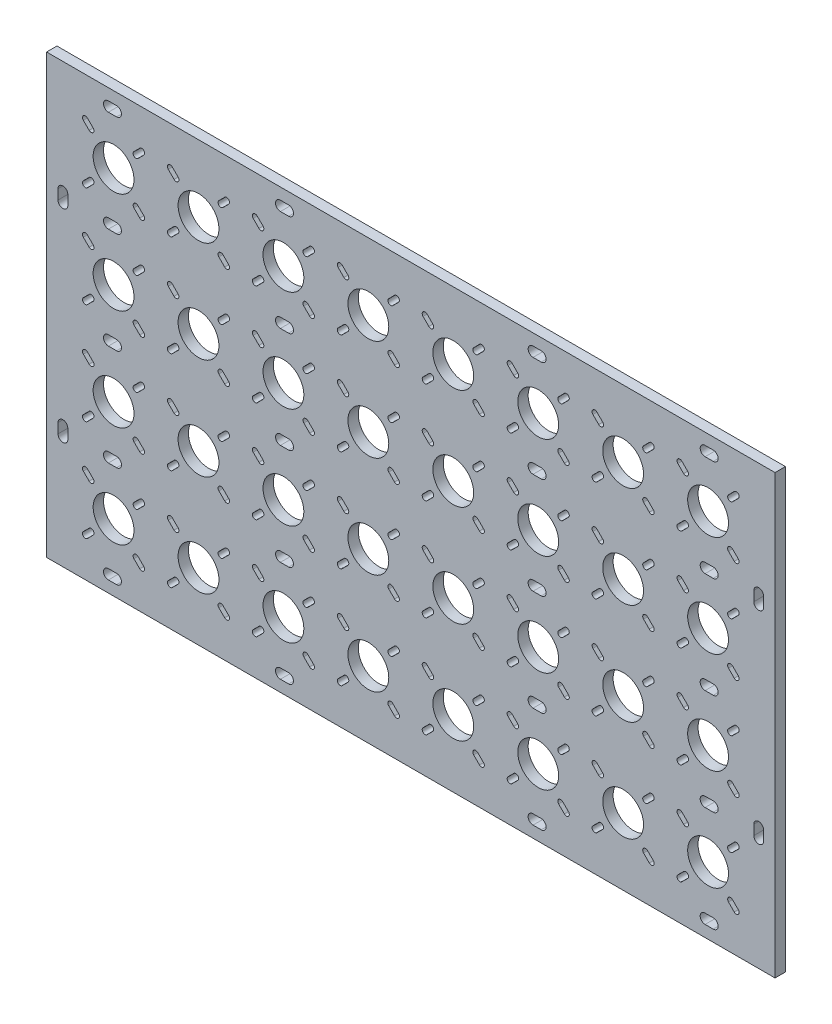
SolidWorks part; units mm, degrees
material "Acrylic (Medium-high impact)"
ref_plane "Front Plane" through (0, 0, 0) normal (0, 0, 1) x (1, 0, 0)
ref_plane "Top Plane" through (0, 0, 0) normal (0, 1, 0) x (1, 0, 0)
ref_plane "Right Plane" through (0, 0, 0) normal (1, 0, 0) x (0, 0, -1)
sketch "Sketch1" plane through (0, 0, 0) normal (0, 0, 1) x (1, 0, 0)
  line L0 (-203, 114) -> (-161, 72) construction
  line L1 (223, -134) -> (-223, -134)
  line L2 (223, -134) -> (223, 134)
  line L3 (223, 134) -> (-223, 134)
  line L4 (-223, -134) -> (-223, 134)
  line L5 (223, -134) -> (-223, 134) construction
  line L6 (223, 134) -> (-223, -134) construction
  line L7 (203, -114) -> (-203, -114) construction
  line L8 (203, -114) -> (203, 114) construction
  line L9 (203, 114) -> (-203, 114) construction
  line L10 (-203, -114) -> (-203, 114) construction
  line L11 (203, -114) -> (-203, 114) construction
  line L12 (203, 114) -> (-203, -114) construction
  line L13 (-203, 114) -> (-161, 114) construction
  line L14 (-203, 114) -> (-203, 72) construction
  line L15 (-203, 72) -> (-161, 72) construction
  line L16 (-161, 114) -> (-161, 72) construction
  line L17 (-203, 72) -> (-161, 114) construction
  line L18 (-199.2678, 110.2678) -> (-195.7322, 106.7322) construction
  line L19 (-166.5, 77.5) -> (-197.5, 77.5) construction
  line L20 (-166.5, 77.5) -> (-166.5, 108.5) construction
  line L21 (-166.5, 108.5) -> (-197.5, 108.5) construction
  line L22 (-197.5, 77.5) -> (-197.5, 108.5) construction
  line L23 (-166.5, 77.5) -> (-197.5, 108.5) construction
  line L24 (-166.5, 108.5) -> (-197.5, 77.5) construction
  line L25 (-198.0303, 111.5052) -> (-194.4948, 107.9697)
  line L26 (-200.5052, 109.0303) -> (-196.9697, 105.4948)
  line L27 (-164.7322, 110.2678) -> (-168.2678, 106.7322) construction
  line L28 (-163.4948, 109.0303) -> (-167.0303, 105.4948)
  line L29 (-165.9697, 111.5052) -> (-169.5052, 107.9697)
  line L30 (-164.7322, 75.7322) -> (-168.2678, 79.2678) construction
  line L31 (-165.9697, 74.4948) -> (-169.5052, 78.0303)
  line L32 (-163.4948, 76.9697) -> (-167.0303, 80.5052)
  line L33 (-199.2678, 75.7322) -> (-195.7322, 79.2678) construction
  line L34 (-200.5052, 76.9697) -> (-196.9697, 80.5052)
  line L35 (-198.0303, 74.4948) -> (-194.4948, 78.0303)
  line L36 (-109, 114) -> (-109, 72) construction
  line L37 (-151, 72) -> (-109, 72) construction
  line L38 (-147.2678, 110.2678) -> (-143.7322, 106.7322) construction
  line L39 (-146.0303, 111.5052) -> (-142.4948, 107.9697)
  line L40 (-148.5052, 109.0303) -> (-144.9697, 105.4948)
  line L41 (-112.7322, 110.2678) -> (-116.2678, 106.7322) construction
  line L42 (-111.4948, 109.0303) -> (-115.0303, 105.4948)
  line L43 (-113.9697, 111.5052) -> (-117.5052, 107.9697)
  line L44 (-112.7322, 75.7322) -> (-116.2678, 79.2678) construction
  line L45 (-113.9697, 74.4948) -> (-117.5052, 78.0303)
  line L46 (-111.4948, 76.9697) -> (-115.0303, 80.5052)
  line L47 (-147.2678, 75.7322) -> (-143.7322, 79.2678) construction
  line L48 (-148.5052, 76.9697) -> (-144.9697, 80.5052)
  line L49 (-146.0303, 74.4948) -> (-142.4948, 78.0303)
  line L50 (-57, 114) -> (-57, 72) construction
  line L51 (-99, 72) -> (-57, 72) construction
  line L52 (-95.2678, 110.2678) -> (-91.7322, 106.7322) construction
  line L53 (-94.0303, 111.5052) -> (-90.4948, 107.9697)
  line L54 (-96.5052, 109.0303) -> (-92.9697, 105.4948)
  line L55 (-60.7322, 110.2678) -> (-64.2678, 106.7322) construction
  line L56 (-59.4948, 109.0303) -> (-63.0303, 105.4948)
  line L57 (-61.9697, 111.5052) -> (-65.5052, 107.9697)
  line L58 (-60.7322, 75.7322) -> (-64.2678, 79.2678) construction
  line L59 (-61.9697, 74.4948) -> (-65.5052, 78.0303)
  line L60 (-59.4948, 76.9697) -> (-63.0303, 80.5052)
  line L61 (-95.2678, 75.7322) -> (-91.7322, 79.2678) construction
  line L62 (-96.5052, 76.9697) -> (-92.9697, 80.5052)
  line L63 (-94.0303, 74.4948) -> (-90.4948, 78.0303)
  line L64 (-5, 114) -> (-5, 72) construction
  line L65 (-47, 72) -> (-5, 72) construction
  line L66 (-43.2678, 110.2678) -> (-39.7322, 106.7322) construction
  line L67 (-42.0303, 111.5052) -> (-38.4948, 107.9697)
  line L68 (-44.5052, 109.0303) -> (-40.9697, 105.4948)
  line L69 (-8.7322, 110.2678) -> (-12.2678, 106.7322) construction
  line L70 (-7.4948, 109.0303) -> (-11.0303, 105.4948)
  line L71 (-9.9697, 111.5052) -> (-13.5052, 107.9697)
  line L72 (-8.7322, 75.7322) -> (-12.2678, 79.2678) construction
  line L73 (-9.9697, 74.4948) -> (-13.5052, 78.0303)
  line L74 (-7.4948, 76.9697) -> (-11.0303, 80.5052)
  line L75 (-43.2678, 75.7322) -> (-39.7322, 79.2678) construction
  line L76 (-44.5052, 76.9697) -> (-40.9697, 80.5052)
  line L77 (-42.0303, 74.4948) -> (-38.4948, 78.0303)
  line L78 (47, 114) -> (47, 72) construction
  line L79 (5, 72) -> (47, 72) construction
  line L80 (8.7322, 110.2678) -> (12.2678, 106.7322) construction
  line L81 (9.9697, 111.5052) -> (13.5052, 107.9697)
  line L82 (7.4948, 109.0303) -> (11.0303, 105.4948)
  line L83 (43.2678, 110.2678) -> (39.7322, 106.7322) construction
  line L84 (44.5052, 109.0303) -> (40.9697, 105.4948)
  line L85 (42.0303, 111.5052) -> (38.4948, 107.9697)
  line L86 (43.2678, 75.7322) -> (39.7322, 79.2678) construction
  line L87 (42.0303, 74.4948) -> (38.4948, 78.0303)
  line L88 (44.5052, 76.9697) -> (40.9697, 80.5052)
  line L89 (8.7322, 75.7322) -> (12.2678, 79.2678) construction
  line L90 (7.4948, 76.9697) -> (11.0303, 80.5052)
  line L91 (9.9697, 74.4948) -> (13.5052, 78.0303)
  line L92 (99, 114) -> (99, 72) construction
  line L93 (57, 72) -> (99, 72) construction
  line L94 (60.7322, 110.2678) -> (64.2678, 106.7322) construction
  line L95 (61.9697, 111.5052) -> (65.5052, 107.9697)
  line L96 (59.4948, 109.0303) -> (63.0303, 105.4948)
  line L97 (95.2678, 110.2678) -> (91.7322, 106.7322) construction
  line L98 (96.5052, 109.0303) -> (92.9697, 105.4948)
  line L99 (94.0303, 111.5052) -> (90.4948, 107.9697)
  line L100 (95.2678, 75.7322) -> (91.7322, 79.2678) construction
  line L101 (94.0303, 74.4948) -> (90.4948, 78.0303)
  line L102 (96.5052, 76.9697) -> (92.9697, 80.5052)
  line L103 (60.7322, 75.7322) -> (64.2678, 79.2678) construction
  line L104 (59.4948, 76.9697) -> (63.0303, 80.5052)
  line L105 (61.9697, 74.4948) -> (65.5052, 78.0303)
  line L106 (151, 114) -> (151, 72) construction
  line L107 (109, 72) -> (151, 72) construction
  line L108 (112.7322, 110.2678) -> (116.2678, 106.7322) construction
  line L109 (113.9697, 111.5052) -> (117.5052, 107.9697)
  line L110 (111.4948, 109.0303) -> (115.0303, 105.4948)
  line L111 (147.2678, 110.2678) -> (143.7322, 106.7322) construction
  line L112 (148.5052, 109.0303) -> (144.9697, 105.4948)
  line L113 (146.0303, 111.5052) -> (142.4948, 107.9697)
  line L114 (147.2678, 75.7322) -> (143.7322, 79.2678) construction
  line L115 (146.0303, 74.4948) -> (142.4948, 78.0303)
  line L116 (148.5052, 76.9697) -> (144.9697, 80.5052)
  line L117 (112.7322, 75.7322) -> (116.2678, 79.2678) construction
  line L118 (111.4948, 76.9697) -> (115.0303, 80.5052)
  line L119 (113.9697, 74.4948) -> (117.5052, 78.0303)
  line L120 (203, 114) -> (203, 72) construction
  line L121 (161, 72) -> (203, 72) construction
  line L122 (164.7322, 110.2678) -> (168.2678, 106.7322) construction
  line L123 (165.9697, 111.5052) -> (169.5052, 107.9697)
  line L124 (163.4948, 109.0303) -> (167.0303, 105.4948)
  line L125 (199.2678, 110.2678) -> (195.7322, 106.7322) construction
  line L126 (200.5052, 109.0303) -> (196.9697, 105.4948)
  line L127 (198.0303, 111.5052) -> (194.4948, 107.9697)
  line L128 (199.2678, 75.7322) -> (195.7322, 79.2678) construction
  line L129 (198.0303, 74.4948) -> (194.4948, 78.0303)
  line L130 (200.5052, 76.9697) -> (196.9697, 80.5052)
  line L131 (164.7322, 75.7322) -> (168.2678, 79.2678) construction
  line L132 (163.4948, 76.9697) -> (167.0303, 80.5052)
  line L133 (165.9697, 74.4948) -> (169.5052, 78.0303)
  line L134 (-109, 52) -> (-109, 10) construction
  line L135 (-151, 10) -> (-109, 10) construction
  line L136 (-147.2678, 48.2678) -> (-143.7322, 44.7322) construction
  line L137 (-146.0303, 49.5052) -> (-142.4948, 45.9697)
  line L138 (-148.5052, 47.0303) -> (-144.9697, 43.4948)
  line L139 (-112.7322, 48.2678) -> (-116.2678, 44.7322) construction
  line L140 (-111.4948, 47.0303) -> (-115.0303, 43.4948)
  line L141 (-113.9697, 49.5052) -> (-117.5052, 45.9697)
  line L142 (-112.7322, 13.7322) -> (-116.2678, 17.2678) construction
  line L143 (-113.9697, 12.4948) -> (-117.5052, 16.0303)
  line L144 (-111.4948, 14.9697) -> (-115.0303, 18.5052)
  line L145 (-147.2678, 13.7322) -> (-143.7322, 17.2678) construction
  line L146 (-148.5052, 14.9697) -> (-144.9697, 18.5052)
  line L147 (-146.0303, 12.4948) -> (-142.4948, 16.0303)
  line L148 (-57, 52) -> (-57, 10) construction
  line L149 (-99, 10) -> (-57, 10) construction
  line L150 (-95.2678, 48.2678) -> (-91.7322, 44.7322) construction
  line L151 (-94.0303, 49.5052) -> (-90.4948, 45.9697)
  line L152 (-96.5052, 47.0303) -> (-92.9697, 43.4948)
  line L153 (-60.7322, 48.2678) -> (-64.2678, 44.7322) construction
  line L154 (-59.4948, 47.0303) -> (-63.0303, 43.4948)
  line L155 (-61.9697, 49.5052) -> (-65.5052, 45.9697)
  line L156 (-60.7322, 13.7322) -> (-64.2678, 17.2678) construction
  line L157 (-61.9697, 12.4948) -> (-65.5052, 16.0303)
  line L158 (-59.4948, 14.9697) -> (-63.0303, 18.5052)
  line L159 (-95.2678, 13.7322) -> (-91.7322, 17.2678) construction
  line L160 (-96.5052, 14.9697) -> (-92.9697, 18.5052)
  line L161 (-94.0303, 12.4948) -> (-90.4948, 16.0303)
  line L162 (-5, 52) -> (-5, 10) construction
  line L163 (-47, 10) -> (-5, 10) construction
  line L164 (-43.2678, 48.2678) -> (-39.7322, 44.7322) construction
  line L165 (-42.0303, 49.5052) -> (-38.4948, 45.9697)
  line L166 (-44.5052, 47.0303) -> (-40.9697, 43.4948)
  line L167 (-8.7322, 48.2678) -> (-12.2678, 44.7322) construction
  line L168 (-7.4948, 47.0303) -> (-11.0303, 43.4948)
  line L169 (-9.9697, 49.5052) -> (-13.5052, 45.9697)
  line L170 (-8.7322, 13.7322) -> (-12.2678, 17.2678) construction
  line L171 (-9.9697, 12.4948) -> (-13.5052, 16.0303)
  line L172 (-7.4948, 14.9697) -> (-11.0303, 18.5052)
  line L173 (-43.2678, 13.7322) -> (-39.7322, 17.2678) construction
  line L174 (-44.5052, 14.9697) -> (-40.9697, 18.5052)
  line L175 (-42.0303, 12.4948) -> (-38.4948, 16.0303)
  line L176 (47, 52) -> (47, 10) construction
  line L177 (5, 10) -> (47, 10) construction
  line L178 (8.7322, 48.2678) -> (12.2678, 44.7322) construction
  line L179 (9.9697, 49.5052) -> (13.5052, 45.9697)
  line L180 (7.4948, 47.0303) -> (11.0303, 43.4948)
  line L181 (43.2678, 48.2678) -> (39.7322, 44.7322) construction
  line L182 (44.5052, 47.0303) -> (40.9697, 43.4948)
  line L183 (42.0303, 49.5052) -> (38.4948, 45.9697)
  line L184 (43.2678, 13.7322) -> (39.7322, 17.2678) construction
  line L185 (42.0303, 12.4948) -> (38.4948, 16.0303)
  line L186 (44.5052, 14.9697) -> (40.9697, 18.5052)
  line L187 (8.7322, 13.7322) -> (12.2678, 17.2678) construction
  line L188 (7.4948, 14.9697) -> (11.0303, 18.5052)
  line L189 (9.9697, 12.4948) -> (13.5052, 16.0303)
  line L190 (99, 52) -> (99, 10) construction
  line L191 (57, 10) -> (99, 10) construction
  line L192 (60.7322, 48.2678) -> (64.2678, 44.7322) construction
  line L193 (61.9697, 49.5052) -> (65.5052, 45.9697)
  line L194 (59.4948, 47.0303) -> (63.0303, 43.4948)
  line L195 (95.2678, 48.2678) -> (91.7322, 44.7322) construction
  line L196 (96.5052, 47.0303) -> (92.9697, 43.4948)
  line L197 (94.0303, 49.5052) -> (90.4948, 45.9697)
  line L198 (95.2678, 13.7322) -> (91.7322, 17.2678) construction
  line L199 (94.0303, 12.4948) -> (90.4948, 16.0303)
  line L200 (96.5052, 14.9697) -> (92.9697, 18.5052)
  line L201 (60.7322, 13.7322) -> (64.2678, 17.2678) construction
  line L202 (59.4948, 14.9697) -> (63.0303, 18.5052)
  line L203 (61.9697, 12.4948) -> (65.5052, 16.0303)
  line L204 (151, 52) -> (151, 10) construction
  line L205 (109, 10) -> (151, 10) construction
  line L206 (112.7322, 48.2678) -> (116.2678, 44.7322) construction
  line L207 (113.9697, 49.5052) -> (117.5052, 45.9697)
  line L208 (111.4948, 47.0303) -> (115.0303, 43.4948)
  line L209 (147.2678, 48.2678) -> (143.7322, 44.7322) construction
  line L210 (148.5052, 47.0303) -> (144.9697, 43.4948)
  line L211 (146.0303, 49.5052) -> (142.4948, 45.9697)
  line L212 (147.2678, 13.7322) -> (143.7322, 17.2678) construction
  line L213 (146.0303, 12.4948) -> (142.4948, 16.0303)
  line L214 (148.5052, 14.9697) -> (144.9697, 18.5052)
  line L215 (112.7322, 13.7322) -> (116.2678, 17.2678) construction
  line L216 (111.4948, 14.9697) -> (115.0303, 18.5052)
  line L217 (113.9697, 12.4948) -> (117.5052, 16.0303)
  line L218 (203, 52) -> (203, 10) construction
  line L219 (161, 10) -> (203, 10) construction
  line L220 (164.7322, 48.2678) -> (168.2678, 44.7322) construction
  line L221 (165.9697, 49.5052) -> (169.5052, 45.9697)
  line L222 (163.4948, 47.0303) -> (167.0303, 43.4948)
  line L223 (199.2678, 48.2678) -> (195.7322, 44.7322) construction
  line L224 (200.5052, 47.0303) -> (196.9697, 43.4948)
  line L225 (198.0303, 49.5052) -> (194.4948, 45.9697)
  line L226 (199.2678, 13.7322) -> (195.7322, 17.2678) construction
  line L227 (198.0303, 12.4948) -> (194.4948, 16.0303)
  line L228 (200.5052, 14.9697) -> (196.9697, 18.5052)
  line L229 (164.7322, 13.7322) -> (168.2678, 17.2678) construction
  line L230 (163.4948, 14.9697) -> (167.0303, 18.5052)
  line L231 (165.9697, 12.4948) -> (169.5052, 16.0303)
  line L232 (-109, -10) -> (-109, -52) construction
  line L233 (-151, -52) -> (-109, -52) construction
  line L234 (-147.2678, -13.7322) -> (-143.7322, -17.2678) construction
  line L235 (-146.0303, -12.4948) -> (-142.4948, -16.0303)
  line L236 (-148.5052, -14.9697) -> (-144.9697, -18.5052)
  line L237 (-112.7322, -13.7322) -> (-116.2678, -17.2678) construction
  line L238 (-111.4948, -14.9697) -> (-115.0303, -18.5052)
  line L239 (-113.9697, -12.4948) -> (-117.5052, -16.0303)
  line L240 (-112.7322, -48.2678) -> (-116.2678, -44.7322) construction
  line L241 (-113.9697, -49.5052) -> (-117.5052, -45.9697)
  line L242 (-111.4948, -47.0303) -> (-115.0303, -43.4948)
  line L243 (-147.2678, -48.2678) -> (-143.7322, -44.7322) construction
  line L244 (-148.5052, -47.0303) -> (-144.9697, -43.4948)
  line L245 (-146.0303, -49.5052) -> (-142.4948, -45.9697)
  line L246 (-57, -10) -> (-57, -52) construction
  line L247 (-99, -52) -> (-57, -52) construction
  line L248 (-95.2678, -13.7322) -> (-91.7322, -17.2678) construction
  line L249 (-94.0303, -12.4948) -> (-90.4948, -16.0303)
  line L250 (-96.5052, -14.9697) -> (-92.9697, -18.5052)
  line L251 (-60.7322, -13.7322) -> (-64.2678, -17.2678) construction
  line L252 (-59.4948, -14.9697) -> (-63.0303, -18.5052)
  line L253 (-61.9697, -12.4948) -> (-65.5052, -16.0303)
  line L254 (-60.7322, -48.2678) -> (-64.2678, -44.7322) construction
  line L255 (-61.9697, -49.5052) -> (-65.5052, -45.9697)
  line L256 (-59.4948, -47.0303) -> (-63.0303, -43.4948)
  line L257 (-95.2678, -48.2678) -> (-91.7322, -44.7322) construction
  line L258 (-96.5052, -47.0303) -> (-92.9697, -43.4948)
  line L259 (-94.0303, -49.5052) -> (-90.4948, -45.9697)
  line L260 (-5, -10) -> (-5, -52) construction
  line L261 (-47, -52) -> (-5, -52) construction
  line L262 (-43.2678, -13.7322) -> (-39.7322, -17.2678) construction
  line L263 (-42.0303, -12.4948) -> (-38.4948, -16.0303)
  line L264 (-44.5052, -14.9697) -> (-40.9697, -18.5052)
  line L265 (-8.7322, -13.7322) -> (-12.2678, -17.2678) construction
  line L266 (-7.4948, -14.9697) -> (-11.0303, -18.5052)
  line L267 (-9.9697, -12.4948) -> (-13.5052, -16.0303)
  line L268 (-8.7322, -48.2678) -> (-12.2678, -44.7322) construction
  line L269 (-9.9697, -49.5052) -> (-13.5052, -45.9697)
  line L270 (-7.4948, -47.0303) -> (-11.0303, -43.4948)
  line L271 (-43.2678, -48.2678) -> (-39.7322, -44.7322) construction
  line L272 (-44.5052, -47.0303) -> (-40.9697, -43.4948)
  line L273 (-42.0303, -49.5052) -> (-38.4948, -45.9697)
  line L274 (47, -10) -> (47, -52) construction
  line L275 (5, -52) -> (47, -52) construction
  line L276 (8.7322, -13.7322) -> (12.2678, -17.2678) construction
  line L277 (9.9697, -12.4948) -> (13.5052, -16.0303)
  line L278 (7.4948, -14.9697) -> (11.0303, -18.5052)
  line L279 (43.2678, -13.7322) -> (39.7322, -17.2678) construction
  line L280 (44.5052, -14.9697) -> (40.9697, -18.5052)
  line L281 (42.0303, -12.4948) -> (38.4948, -16.0303)
  line L282 (43.2678, -48.2678) -> (39.7322, -44.7322) construction
  line L283 (42.0303, -49.5052) -> (38.4948, -45.9697)
  line L284 (44.5052, -47.0303) -> (40.9697, -43.4948)
  line L285 (8.7322, -48.2678) -> (12.2678, -44.7322) construction
  line L286 (7.4948, -47.0303) -> (11.0303, -43.4948)
  line L287 (9.9697, -49.5052) -> (13.5052, -45.9697)
  line L288 (99, -10) -> (99, -52) construction
  line L289 (57, -52) -> (99, -52) construction
  line L290 (60.7322, -13.7322) -> (64.2678, -17.2678) construction
  line L291 (61.9697, -12.4948) -> (65.5052, -16.0303)
  line L292 (59.4948, -14.9697) -> (63.0303, -18.5052)
  line L293 (95.2678, -13.7322) -> (91.7322, -17.2678) construction
  line L294 (96.5052, -14.9697) -> (92.9697, -18.5052)
  line L295 (94.0303, -12.4948) -> (90.4948, -16.0303)
  line L296 (95.2678, -48.2678) -> (91.7322, -44.7322) construction
  line L297 (94.0303, -49.5052) -> (90.4948, -45.9697)
  line L298 (96.5052, -47.0303) -> (92.9697, -43.4948)
  line L299 (60.7322, -48.2678) -> (64.2678, -44.7322) construction
  line L300 (59.4948, -47.0303) -> (63.0303, -43.4948)
  line L301 (61.9697, -49.5052) -> (65.5052, -45.9697)
  line L302 (151, -10) -> (151, -52) construction
  line L303 (109, -52) -> (151, -52) construction
  line L304 (112.7322, -13.7322) -> (116.2678, -17.2678) construction
  line L305 (113.9697, -12.4948) -> (117.5052, -16.0303)
  line L306 (111.4948, -14.9697) -> (115.0303, -18.5052)
  line L307 (147.2678, -13.7322) -> (143.7322, -17.2678) construction
  line L308 (148.5052, -14.9697) -> (144.9697, -18.5052)
  line L309 (146.0303, -12.4948) -> (142.4948, -16.0303)
  line L310 (147.2678, -48.2678) -> (143.7322, -44.7322) construction
  line L311 (146.0303, -49.5052) -> (142.4948, -45.9697)
  line L312 (148.5052, -47.0303) -> (144.9697, -43.4948)
  line L313 (112.7322, -48.2678) -> (116.2678, -44.7322) construction
  line L314 (111.4948, -47.0303) -> (115.0303, -43.4948)
  line L315 (113.9697, -49.5052) -> (117.5052, -45.9697)
  line L316 (203, -10) -> (203, -52) construction
  line L317 (161, -52) -> (203, -52) construction
  line L318 (164.7322, -13.7322) -> (168.2678, -17.2678) construction
  line L319 (165.9697, -12.4948) -> (169.5052, -16.0303)
  line L320 (163.4948, -14.9697) -> (167.0303, -18.5052)
  line L321 (199.2678, -13.7322) -> (195.7322, -17.2678) construction
  line L322 (200.5052, -14.9697) -> (196.9697, -18.5052)
  line L323 (198.0303, -12.4948) -> (194.4948, -16.0303)
  line L324 (199.2678, -48.2678) -> (195.7322, -44.7322) construction
  line L325 (198.0303, -49.5052) -> (194.4948, -45.9697)
  line L326 (200.5052, -47.0303) -> (196.9697, -43.4948)
  line L327 (164.7322, -48.2678) -> (168.2678, -44.7322) construction
  line L328 (163.4948, -47.0303) -> (167.0303, -43.4948)
  line L329 (165.9697, -49.5052) -> (169.5052, -45.9697)
  line L330 (-109, -72) -> (-109, -114) construction
  line L331 (-151, -114) -> (-109, -114) construction
  line L332 (-147.2678, -75.7322) -> (-143.7322, -79.2678) construction
  line L333 (-146.0303, -74.4948) -> (-142.4948, -78.0303)
  line L334 (-148.5052, -76.9697) -> (-144.9697, -80.5052)
  line L335 (-112.7322, -75.7322) -> (-116.2678, -79.2678) construction
  line L336 (-111.4948, -76.9697) -> (-115.0303, -80.5052)
  line L337 (-113.9697, -74.4948) -> (-117.5052, -78.0303)
  line L338 (-112.7322, -110.2678) -> (-116.2678, -106.7322) construction
  line L339 (-113.9697, -111.5052) -> (-117.5052, -107.9697)
  line L340 (-111.4948, -109.0303) -> (-115.0303, -105.4948)
  line L341 (-147.2678, -110.2678) -> (-143.7322, -106.7322) construction
  line L342 (-148.5052, -109.0303) -> (-144.9697, -105.4948)
  line L343 (-146.0303, -111.5052) -> (-142.4948, -107.9697)
  line L344 (-57, -72) -> (-57, -114) construction
  line L345 (-99, -114) -> (-57, -114) construction
  line L346 (-95.2678, -75.7322) -> (-91.7322, -79.2678) construction
  line L347 (-94.0303, -74.4948) -> (-90.4948, -78.0303)
  line L348 (-96.5052, -76.9697) -> (-92.9697, -80.5052)
  line L349 (-60.7322, -75.7322) -> (-64.2678, -79.2678) construction
  line L350 (-59.4948, -76.9697) -> (-63.0303, -80.5052)
  line L351 (-61.9697, -74.4948) -> (-65.5052, -78.0303)
  line L352 (-60.7322, -110.2678) -> (-64.2678, -106.7322) construction
  line L353 (-61.9697, -111.5052) -> (-65.5052, -107.9697)
  line L354 (-59.4948, -109.0303) -> (-63.0303, -105.4948)
  line L355 (-95.2678, -110.2678) -> (-91.7322, -106.7322) construction
  line L356 (-96.5052, -109.0303) -> (-92.9697, -105.4948)
  line L357 (-94.0303, -111.5052) -> (-90.4948, -107.9697)
  line L358 (-5, -72) -> (-5, -114) construction
  line L359 (-47, -114) -> (-5, -114) construction
  line L360 (-43.2678, -75.7322) -> (-39.7322, -79.2678) construction
  line L361 (-42.0303, -74.4948) -> (-38.4948, -78.0303)
  line L362 (-44.5052, -76.9697) -> (-40.9697, -80.5052)
  line L363 (-8.7322, -75.7322) -> (-12.2678, -79.2678) construction
  line L364 (-7.4948, -76.9697) -> (-11.0303, -80.5052)
  line L365 (-9.9697, -74.4948) -> (-13.5052, -78.0303)
  line L366 (-8.7322, -110.2678) -> (-12.2678, -106.7322) construction
  line L367 (-9.9697, -111.5052) -> (-13.5052, -107.9697)
  line L368 (-7.4948, -109.0303) -> (-11.0303, -105.4948)
  line L369 (-43.2678, -110.2678) -> (-39.7322, -106.7322) construction
  line L370 (-44.5052, -109.0303) -> (-40.9697, -105.4948)
  line L371 (-42.0303, -111.5052) -> (-38.4948, -107.9697)
  line L372 (47, -72) -> (47, -114) construction
  line L373 (5, -114) -> (47, -114) construction
  line L374 (8.7322, -75.7322) -> (12.2678, -79.2678) construction
  line L375 (9.9697, -74.4948) -> (13.5052, -78.0303)
  line L376 (7.4948, -76.9697) -> (11.0303, -80.5052)
  line L377 (43.2678, -75.7322) -> (39.7322, -79.2678) construction
  line L378 (44.5052, -76.9697) -> (40.9697, -80.5052)
  line L379 (42.0303, -74.4948) -> (38.4948, -78.0303)
  line L380 (43.2678, -110.2678) -> (39.7322, -106.7322) construction
  line L381 (42.0303, -111.5052) -> (38.4948, -107.9697)
  line L382 (44.5052, -109.0303) -> (40.9697, -105.4948)
  line L383 (8.7322, -110.2678) -> (12.2678, -106.7322) construction
  line L384 (7.4948, -109.0303) -> (11.0303, -105.4948)
  line L385 (9.9697, -111.5052) -> (13.5052, -107.9697)
  line L386 (99, -72) -> (99, -114) construction
  line L387 (57, -114) -> (99, -114) construction
  line L388 (60.7322, -75.7322) -> (64.2678, -79.2678) construction
  line L389 (61.9697, -74.4948) -> (65.5052, -78.0303)
  line L390 (59.4948, -76.9697) -> (63.0303, -80.5052)
  line L391 (95.2678, -75.7322) -> (91.7322, -79.2678) construction
  line L392 (96.5052, -76.9697) -> (92.9697, -80.5052)
  line L393 (94.0303, -74.4948) -> (90.4948, -78.0303)
  line L394 (95.2678, -110.2678) -> (91.7322, -106.7322) construction
  line L395 (94.0303, -111.5052) -> (90.4948, -107.9697)
  line L396 (96.5052, -109.0303) -> (92.9697, -105.4948)
  line L397 (60.7322, -110.2678) -> (64.2678, -106.7322) construction
  line L398 (59.4948, -109.0303) -> (63.0303, -105.4948)
  line L399 (61.9697, -111.5052) -> (65.5052, -107.9697)
  line L400 (151, -72) -> (151, -114) construction
  line L401 (109, -114) -> (151, -114) construction
  line L402 (112.7322, -75.7322) -> (116.2678, -79.2678) construction
  line L403 (113.9697, -74.4948) -> (117.5052, -78.0303)
  line L404 (111.4948, -76.9697) -> (115.0303, -80.5052)
  line L405 (147.2678, -75.7322) -> (143.7322, -79.2678) construction
  line L406 (148.5052, -76.9697) -> (144.9697, -80.5052)
  line L407 (146.0303, -74.4948) -> (142.4948, -78.0303)
  line L408 (147.2678, -110.2678) -> (143.7322, -106.7322) construction
  line L409 (146.0303, -111.5052) -> (142.4948, -107.9697)
  line L410 (148.5052, -109.0303) -> (144.9697, -105.4948)
  line L411 (112.7322, -110.2678) -> (116.2678, -106.7322) construction
  line L412 (111.4948, -109.0303) -> (115.0303, -105.4948)
  line L413 (113.9697, -111.5052) -> (117.5052, -107.9697)
  line L414 (203, -72) -> (203, -114) construction
  line L415 (161, -114) -> (203, -114) construction
  line L416 (164.7322, -75.7322) -> (168.2678, -79.2678) construction
  line L417 (165.9697, -74.4948) -> (169.5052, -78.0303)
  line L418 (163.4948, -76.9697) -> (167.0303, -80.5052)
  line L419 (199.2678, -75.7322) -> (195.7322, -79.2678) construction
  line L420 (200.5052, -76.9697) -> (196.9697, -80.5052)
  line L421 (198.0303, -74.4948) -> (194.4948, -78.0303)
  line L422 (199.2678, -110.2678) -> (195.7322, -106.7322) construction
  line L423 (198.0303, -111.5052) -> (194.4948, -107.9697)
  line L424 (200.5052, -109.0303) -> (196.9697, -105.4948)
  line L425 (164.7322, -110.2678) -> (168.2678, -106.7322) construction
  line L426 (163.4948, -109.0303) -> (167.0303, -105.4948)
  line L427 (165.9697, -111.5052) -> (169.5052, -107.9697)
  line L428 (-161, 52) -> (-161, 10) construction
  line L429 (-203, 10) -> (-161, 10) construction
  line L430 (-199.2678, 48.2678) -> (-195.7322, 44.7322) construction
  line L431 (-198.0303, 49.5052) -> (-194.4948, 45.9697)
  line L432 (-200.5052, 47.0303) -> (-196.9697, 43.4948)
  line L433 (-164.7322, 48.2678) -> (-168.2678, 44.7322) construction
  line L434 (-163.4948, 47.0303) -> (-167.0303, 43.4948)
  line L435 (-165.9697, 49.5052) -> (-169.5052, 45.9697)
  line L436 (-164.7322, 13.7322) -> (-168.2678, 17.2678) construction
  line L437 (-165.9697, 12.4948) -> (-169.5052, 16.0303)
  line L438 (-163.4948, 14.9697) -> (-167.0303, 18.5052)
  line L439 (-199.2678, 13.7322) -> (-195.7322, 17.2678) construction
  line L440 (-200.5052, 14.9697) -> (-196.9697, 18.5052)
  line L441 (-198.0303, 12.4948) -> (-194.4948, 16.0303)
  line L442 (-161, -10) -> (-161, -52) construction
  line L443 (-203, -52) -> (-161, -52) construction
  line L444 (-199.2678, -13.7322) -> (-195.7322, -17.2678) construction
  line L445 (-198.0303, -12.4948) -> (-194.4948, -16.0303)
  line L446 (-200.5052, -14.9697) -> (-196.9697, -18.5052)
  line L447 (-164.7322, -13.7322) -> (-168.2678, -17.2678) construction
  line L448 (-163.4948, -14.9697) -> (-167.0303, -18.5052)
  line L449 (-165.9697, -12.4948) -> (-169.5052, -16.0303)
  line L450 (-164.7322, -48.2678) -> (-168.2678, -44.7322) construction
  line L451 (-165.9697, -49.5052) -> (-169.5052, -45.9697)
  line L452 (-163.4948, -47.0303) -> (-167.0303, -43.4948)
  line L453 (-199.2678, -48.2678) -> (-195.7322, -44.7322) construction
  line L454 (-200.5052, -47.0303) -> (-196.9697, -43.4948)
  line L455 (-198.0303, -49.5052) -> (-194.4948, -45.9697)
  line L456 (-161, -72) -> (-161, -114) construction
  line L457 (-203, -114) -> (-161, -114) construction
  line L458 (-199.2678, -75.7322) -> (-195.7322, -79.2678) construction
  line L459 (-198.0303, -74.4948) -> (-194.4948, -78.0303)
  line L460 (-200.5052, -76.9697) -> (-196.9697, -80.5052)
  line L461 (-164.7322, -75.7322) -> (-168.2678, -79.2678) construction
  line L462 (-163.4948, -76.9697) -> (-167.0303, -80.5052)
  line L463 (-165.9697, -74.4948) -> (-169.5052, -78.0303)
  line L464 (-164.7322, -110.2678) -> (-168.2678, -106.7322) construction
  line L465 (-165.9697, -111.5052) -> (-169.5052, -107.9697)
  line L466 (-163.4948, -109.0303) -> (-167.0303, -105.4948)
  line L467 (-199.2678, -110.2678) -> (-195.7322, -106.7322) construction
  line L468 (-200.5052, -109.0303) -> (-196.9697, -105.4948)
  line L469 (-198.0303, -111.5052) -> (-194.4948, -107.9697)
  line L470 (-185.1645, 124) -> (-180.1645, 124) construction
  line L471 (213, -124) -> (-213, -124) construction
  line L472 (213, -124) -> (213, 124) construction
  line L473 (213, 124) -> (-213, 124) construction
  line L474 (-213, -124) -> (-213, 124) construction
  line L475 (213, -124) -> (-213, 124) construction
  line L476 (213, 124) -> (-213, -124) construction
  line L477 (-185.1645, 127) -> (-180.1645, 127)
  line L478 (-185.1645, 121) -> (-180.1645, 121)
  line L479 (-182, 93) -> (-182, 88.4154) construction
  line L480 (-182, 93) -> (-177.9536, 93) construction
  line L481 (-130, 93) -> (-130, 88.4154) construction
  line L482 (-74.8355, 124) -> (-79.8355, 124) construction
  line L483 (-74.8355, 127) -> (-79.8355, 127)
  line L484 (-74.8355, 121) -> (-79.8355, 121)
  line L485 (0, 10) -> (0, -7.4331) construction
  line L486 (-7.4948, 0) -> (6.3552, 0) construction
  line L487 (74.8355, 124) -> (79.8355, 124) construction
  line L488 (74.8355, 127) -> (79.8355, 127)
  line L489 (74.8355, 121) -> (79.8355, 121)
  line L490 (185.1645, 124) -> (180.1645, 124) construction
  line L491 (185.1645, 127) -> (180.1645, 127)
  line L492 (185.1645, 121) -> (180.1645, 121)
  line L493 (185.1645, 62) -> (180.1645, 62) construction
  line L494 (185.1645, 59) -> (180.1645, 59)
  line L495 (185.1645, 65) -> (180.1645, 65)
  line L496 (74.8355, 62) -> (79.8355, 62) construction
  line L497 (74.8355, 59) -> (79.8355, 59)
  line L498 (74.8355, 65) -> (79.8355, 65)
  line L499 (-74.8355, 62) -> (-79.8355, 62) construction
  line L500 (-74.8355, 59) -> (-79.8355, 59)
  line L501 (-74.8355, 65) -> (-79.8355, 65)
  line L502 (-185.1645, 62) -> (-180.1645, 62) construction
  line L503 (-185.1645, 59) -> (-180.1645, 59)
  line L504 (-185.1645, 65) -> (-180.1645, 65)
  line L505 (-182, 31) -> (-176.1897, 31) construction
  line L506 (185.1645, 0) -> (180.1645, 0) construction
  line L507 (185.1645, 3) -> (180.1645, 3)
  line L508 (185.1645, -3) -> (180.1645, -3)
  line L509 (74.8355, 0) -> (79.8355, 0) construction
  line L510 (74.8355, 3) -> (79.8355, 3)
  line L511 (74.8355, -3) -> (79.8355, -3)
  line L512 (-74.8355, 0) -> (-79.8355, 0) construction
  line L513 (-74.8355, 3) -> (-79.8355, 3)
  line L514 (-74.8355, -3) -> (-79.8355, -3)
  line L515 (-185.1645, 0) -> (-180.1645, 0) construction
  line L516 (-185.1645, 3) -> (-180.1645, 3)
  line L517 (-185.1645, -3) -> (-180.1645, -3)
  line L518 (185.1645, -62) -> (180.1645, -62) construction
  line L519 (185.1645, -59) -> (180.1645, -59)
  line L520 (185.1645, -65) -> (180.1645, -65)
  line L521 (74.8355, -62) -> (79.8355, -62) construction
  line L522 (74.8355, -59) -> (79.8355, -59)
  line L523 (74.8355, -65) -> (79.8355, -65)
  line L524 (-74.8355, -62) -> (-79.8355, -62) construction
  line L525 (-74.8355, -59) -> (-79.8355, -59)
  line L526 (-74.8355, -65) -> (-79.8355, -65)
  line L527 (-185.1645, -62) -> (-180.1645, -62) construction
  line L528 (-185.1645, -59) -> (-180.1645, -59)
  line L529 (-185.1645, -65) -> (-180.1645, -65)
  line L530 (185.1645, -124) -> (180.1645, -124) construction
  line L531 (185.1645, -127) -> (180.1645, -127)
  line L532 (185.1645, -121) -> (180.1645, -121)
  line L533 (74.8355, -124) -> (79.8355, -124) construction
  line L534 (74.8355, -127) -> (79.8355, -127)
  line L535 (74.8355, -121) -> (79.8355, -121)
  line L536 (-74.8355, -124) -> (-79.8355, -124) construction
  line L537 (-74.8355, -127) -> (-79.8355, -127)
  line L538 (-74.8355, -121) -> (-79.8355, -121)
  line L539 (-185.1645, -124) -> (-180.1645, -124) construction
  line L540 (-185.1645, -127) -> (-180.1645, -127)
  line L541 (-185.1645, -121) -> (-180.1645, -121)
  line L542 (-213, 59) -> (-213, 65) construction
  line L543 (-216, 59) -> (-216, 65)
  line L544 (-210, 59) -> (-210, 65)
  line L545 (-213, -59) -> (-213, -65) construction
  line L546 (-216, -59) -> (-216, -65)
  line L547 (-210, -59) -> (-210, -65)
  line L548 (213, 59) -> (213, 65) construction
  line L549 (216, 59) -> (216, 65)
  line L550 (210, 59) -> (210, 65)
  line L551 (213, -59) -> (213, -65) construction
  line L552 (216, -59) -> (216, -65)
  line L553 (210, -59) -> (210, -65)
  circle A0 centre (-182, 93) radius 12.5
  arc A5 (-198.0303, 111.5052) -> (-200.5052, 109.0303) centre (-199.2678, 110.2678) ccw
  arc A6 (-196.9697, 105.4948) -> (-194.4948, 107.9697) centre (-195.7322, 106.7322) ccw
  arc A7 (-163.4948, 109.0303) -> (-165.9697, 111.5052) centre (-164.7322, 110.2678) ccw
  arc A8 (-169.5052, 107.9697) -> (-167.0303, 105.4948) centre (-168.2678, 106.7322) ccw
  arc A9 (-165.9697, 74.4948) -> (-163.4948, 76.9697) centre (-164.7322, 75.7322) ccw
  arc A10 (-167.0303, 80.5052) -> (-169.5052, 78.0303) centre (-168.2678, 79.2678) ccw
  arc A11 (-200.5052, 76.9697) -> (-198.0303, 74.4948) centre (-199.2678, 75.7322) ccw
  arc A12 (-194.4948, 78.0303) -> (-196.9697, 80.5052) centre (-195.7322, 79.2678) ccw
  circle A13 centre (-130, 93) radius 12.5
  arc A14 (-146.0303, 111.5052) -> (-148.5052, 109.0303) centre (-147.2678, 110.2678) ccw
  arc A15 (-144.9697, 105.4948) -> (-142.4948, 107.9697) centre (-143.7322, 106.7322) ccw
  arc A16 (-111.4948, 109.0303) -> (-113.9697, 111.5052) centre (-112.7322, 110.2678) ccw
  arc A17 (-117.5052, 107.9697) -> (-115.0303, 105.4948) centre (-116.2678, 106.7322) ccw
  arc A18 (-113.9697, 74.4948) -> (-111.4948, 76.9697) centre (-112.7322, 75.7322) ccw
  arc A19 (-115.0303, 80.5052) -> (-117.5052, 78.0303) centre (-116.2678, 79.2678) ccw
  arc A20 (-148.5052, 76.9697) -> (-146.0303, 74.4948) centre (-147.2678, 75.7322) ccw
  arc A21 (-142.4948, 78.0303) -> (-144.9697, 80.5052) centre (-143.7322, 79.2678) ccw
  circle A22 centre (-78, 93) radius 12.5
  arc A23 (-94.0303, 111.5052) -> (-96.5052, 109.0303) centre (-95.2678, 110.2678) ccw
  arc A24 (-92.9697, 105.4948) -> (-90.4948, 107.9697) centre (-91.7322, 106.7322) ccw
  arc A25 (-59.4948, 109.0303) -> (-61.9697, 111.5052) centre (-60.7322, 110.2678) ccw
  arc A26 (-65.5052, 107.9697) -> (-63.0303, 105.4948) centre (-64.2678, 106.7322) ccw
  arc A27 (-61.9697, 74.4948) -> (-59.4948, 76.9697) centre (-60.7322, 75.7322) ccw
  arc A28 (-63.0303, 80.5052) -> (-65.5052, 78.0303) centre (-64.2678, 79.2678) ccw
  arc A29 (-96.5052, 76.9697) -> (-94.0303, 74.4948) centre (-95.2678, 75.7322) ccw
  arc A30 (-90.4948, 78.0303) -> (-92.9697, 80.5052) centre (-91.7322, 79.2678) ccw
  circle A31 centre (-26, 93) radius 12.5
  arc A32 (-42.0303, 111.5052) -> (-44.5052, 109.0303) centre (-43.2678, 110.2678) ccw
  arc A33 (-40.9697, 105.4948) -> (-38.4948, 107.9697) centre (-39.7322, 106.7322) ccw
  arc A34 (-7.4948, 109.0303) -> (-9.9697, 111.5052) centre (-8.7322, 110.2678) ccw
  arc A35 (-13.5052, 107.9697) -> (-11.0303, 105.4948) centre (-12.2678, 106.7322) ccw
  arc A36 (-9.9697, 74.4948) -> (-7.4948, 76.9697) centre (-8.7322, 75.7322) ccw
  arc A37 (-11.0303, 80.5052) -> (-13.5052, 78.0303) centre (-12.2678, 79.2678) ccw
  arc A38 (-44.5052, 76.9697) -> (-42.0303, 74.4948) centre (-43.2678, 75.7322) ccw
  arc A39 (-38.4948, 78.0303) -> (-40.9697, 80.5052) centre (-39.7322, 79.2678) ccw
  circle A40 centre (26, 93) radius 12.5
  arc A41 (9.9697, 111.5052) -> (7.4948, 109.0303) centre (8.7322, 110.2678) ccw
  arc A42 (11.0303, 105.4948) -> (13.5052, 107.9697) centre (12.2678, 106.7322) ccw
  arc A43 (44.5052, 109.0303) -> (42.0303, 111.5052) centre (43.2678, 110.2678) ccw
  arc A44 (38.4948, 107.9697) -> (40.9697, 105.4948) centre (39.7322, 106.7322) ccw
  arc A45 (42.0303, 74.4948) -> (44.5052, 76.9697) centre (43.2678, 75.7322) ccw
  arc A46 (40.9697, 80.5052) -> (38.4948, 78.0303) centre (39.7322, 79.2678) ccw
  arc A47 (7.4948, 76.9697) -> (9.9697, 74.4948) centre (8.7322, 75.7322) ccw
  arc A48 (13.5052, 78.0303) -> (11.0303, 80.5052) centre (12.2678, 79.2678) ccw
  circle A49 centre (78, 93) radius 12.5
  arc A50 (61.9697, 111.5052) -> (59.4948, 109.0303) centre (60.7322, 110.2678) ccw
  arc A51 (63.0303, 105.4948) -> (65.5052, 107.9697) centre (64.2678, 106.7322) ccw
  arc A52 (96.5052, 109.0303) -> (94.0303, 111.5052) centre (95.2678, 110.2678) ccw
  arc A53 (90.4948, 107.9697) -> (92.9697, 105.4948) centre (91.7322, 106.7322) ccw
  arc A54 (94.0303, 74.4948) -> (96.5052, 76.9697) centre (95.2678, 75.7322) ccw
  arc A55 (92.9697, 80.5052) -> (90.4948, 78.0303) centre (91.7322, 79.2678) ccw
  arc A56 (59.4948, 76.9697) -> (61.9697, 74.4948) centre (60.7322, 75.7322) ccw
  arc A57 (65.5052, 78.0303) -> (63.0303, 80.5052) centre (64.2678, 79.2678) ccw
  circle A58 centre (130, 93) radius 12.5
  arc A59 (113.9697, 111.5052) -> (111.4948, 109.0303) centre (112.7322, 110.2678) ccw
  arc A60 (115.0303, 105.4948) -> (117.5052, 107.9697) centre (116.2678, 106.7322) ccw
  arc A61 (148.5052, 109.0303) -> (146.0303, 111.5052) centre (147.2678, 110.2678) ccw
  arc A62 (142.4948, 107.9697) -> (144.9697, 105.4948) centre (143.7322, 106.7322) ccw
  arc A63 (146.0303, 74.4948) -> (148.5052, 76.9697) centre (147.2678, 75.7322) ccw
  arc A64 (144.9697, 80.5052) -> (142.4948, 78.0303) centre (143.7322, 79.2678) ccw
  arc A65 (111.4948, 76.9697) -> (113.9697, 74.4948) centre (112.7322, 75.7322) ccw
  arc A66 (117.5052, 78.0303) -> (115.0303, 80.5052) centre (116.2678, 79.2678) ccw
  circle A67 centre (182, 93) radius 12.5
  arc A68 (165.9697, 111.5052) -> (163.4948, 109.0303) centre (164.7322, 110.2678) ccw
  arc A69 (167.0303, 105.4948) -> (169.5052, 107.9697) centre (168.2678, 106.7322) ccw
  arc A70 (200.5052, 109.0303) -> (198.0303, 111.5052) centre (199.2678, 110.2678) ccw
  arc A71 (194.4948, 107.9697) -> (196.9697, 105.4948) centre (195.7322, 106.7322) ccw
  arc A72 (198.0303, 74.4948) -> (200.5052, 76.9697) centre (199.2678, 75.7322) ccw
  arc A73 (196.9697, 80.5052) -> (194.4948, 78.0303) centre (195.7322, 79.2678) ccw
  arc A74 (163.4948, 76.9697) -> (165.9697, 74.4948) centre (164.7322, 75.7322) ccw
  arc A75 (169.5052, 78.0303) -> (167.0303, 80.5052) centre (168.2678, 79.2678) ccw
  circle A76 centre (-130, 31) radius 12.5
  arc A77 (-146.0303, 49.5052) -> (-148.5052, 47.0303) centre (-147.2678, 48.2678) ccw
  arc A78 (-144.9697, 43.4948) -> (-142.4948, 45.9697) centre (-143.7322, 44.7322) ccw
  arc A79 (-111.4948, 47.0303) -> (-113.9697, 49.5052) centre (-112.7322, 48.2678) ccw
  arc A80 (-117.5052, 45.9697) -> (-115.0303, 43.4948) centre (-116.2678, 44.7322) ccw
  arc A81 (-113.9697, 12.4948) -> (-111.4948, 14.9697) centre (-112.7322, 13.7322) ccw
  arc A82 (-115.0303, 18.5052) -> (-117.5052, 16.0303) centre (-116.2678, 17.2678) ccw
  arc A83 (-148.5052, 14.9697) -> (-146.0303, 12.4948) centre (-147.2678, 13.7322) ccw
  arc A84 (-142.4948, 16.0303) -> (-144.9697, 18.5052) centre (-143.7322, 17.2678) ccw
  circle A85 centre (-78, 31) radius 12.5
  arc A86 (-94.0303, 49.5052) -> (-96.5052, 47.0303) centre (-95.2678, 48.2678) ccw
  arc A87 (-92.9697, 43.4948) -> (-90.4948, 45.9697) centre (-91.7322, 44.7322) ccw
  arc A88 (-59.4948, 47.0303) -> (-61.9697, 49.5052) centre (-60.7322, 48.2678) ccw
  arc A89 (-65.5052, 45.9697) -> (-63.0303, 43.4948) centre (-64.2678, 44.7322) ccw
  arc A90 (-61.9697, 12.4948) -> (-59.4948, 14.9697) centre (-60.7322, 13.7322) ccw
  arc A91 (-63.0303, 18.5052) -> (-65.5052, 16.0303) centre (-64.2678, 17.2678) ccw
  arc A92 (-96.5052, 14.9697) -> (-94.0303, 12.4948) centre (-95.2678, 13.7322) ccw
  arc A93 (-90.4948, 16.0303) -> (-92.9697, 18.5052) centre (-91.7322, 17.2678) ccw
  circle A94 centre (-26, 31) radius 12.5
  arc A95 (-42.0303, 49.5052) -> (-44.5052, 47.0303) centre (-43.2678, 48.2678) ccw
  arc A96 (-40.9697, 43.4948) -> (-38.4948, 45.9697) centre (-39.7322, 44.7322) ccw
  arc A97 (-7.4948, 47.0303) -> (-9.9697, 49.5052) centre (-8.7322, 48.2678) ccw
  arc A98 (-13.5052, 45.9697) -> (-11.0303, 43.4948) centre (-12.2678, 44.7322) ccw
  arc A99 (-9.9697, 12.4948) -> (-7.4948, 14.9697) centre (-8.7322, 13.7322) ccw
  arc A100 (-11.0303, 18.5052) -> (-13.5052, 16.0303) centre (-12.2678, 17.2678) ccw
  arc A101 (-44.5052, 14.9697) -> (-42.0303, 12.4948) centre (-43.2678, 13.7322) ccw
  arc A102 (-38.4948, 16.0303) -> (-40.9697, 18.5052) centre (-39.7322, 17.2678) ccw
  circle A103 centre (26, 31) radius 12.5
  arc A104 (9.9697, 49.5052) -> (7.4948, 47.0303) centre (8.7322, 48.2678) ccw
  arc A105 (11.0303, 43.4948) -> (13.5052, 45.9697) centre (12.2678, 44.7322) ccw
  arc A106 (44.5052, 47.0303) -> (42.0303, 49.5052) centre (43.2678, 48.2678) ccw
  arc A107 (38.4948, 45.9697) -> (40.9697, 43.4948) centre (39.7322, 44.7322) ccw
  arc A108 (42.0303, 12.4948) -> (44.5052, 14.9697) centre (43.2678, 13.7322) ccw
  arc A109 (40.9697, 18.5052) -> (38.4948, 16.0303) centre (39.7322, 17.2678) ccw
  arc A110 (7.4948, 14.9697) -> (9.9697, 12.4948) centre (8.7322, 13.7322) ccw
  arc A111 (13.5052, 16.0303) -> (11.0303, 18.5052) centre (12.2678, 17.2678) ccw
  circle A112 centre (78, 31) radius 12.5
  arc A113 (61.9697, 49.5052) -> (59.4948, 47.0303) centre (60.7322, 48.2678) ccw
  arc A114 (63.0303, 43.4948) -> (65.5052, 45.9697) centre (64.2678, 44.7322) ccw
  arc A115 (96.5052, 47.0303) -> (94.0303, 49.5052) centre (95.2678, 48.2678) ccw
  arc A116 (90.4948, 45.9697) -> (92.9697, 43.4948) centre (91.7322, 44.7322) ccw
  arc A117 (94.0303, 12.4948) -> (96.5052, 14.9697) centre (95.2678, 13.7322) ccw
  arc A118 (92.9697, 18.5052) -> (90.4948, 16.0303) centre (91.7322, 17.2678) ccw
  arc A119 (59.4948, 14.9697) -> (61.9697, 12.4948) centre (60.7322, 13.7322) ccw
  arc A120 (65.5052, 16.0303) -> (63.0303, 18.5052) centre (64.2678, 17.2678) ccw
  circle A121 centre (130, 31) radius 12.5
  arc A122 (113.9697, 49.5052) -> (111.4948, 47.0303) centre (112.7322, 48.2678) ccw
  arc A123 (115.0303, 43.4948) -> (117.5052, 45.9697) centre (116.2678, 44.7322) ccw
  arc A124 (148.5052, 47.0303) -> (146.0303, 49.5052) centre (147.2678, 48.2678) ccw
  arc A125 (142.4948, 45.9697) -> (144.9697, 43.4948) centre (143.7322, 44.7322) ccw
  arc A126 (146.0303, 12.4948) -> (148.5052, 14.9697) centre (147.2678, 13.7322) ccw
  arc A127 (144.9697, 18.5052) -> (142.4948, 16.0303) centre (143.7322, 17.2678) ccw
  arc A128 (111.4948, 14.9697) -> (113.9697, 12.4948) centre (112.7322, 13.7322) ccw
  arc A129 (117.5052, 16.0303) -> (115.0303, 18.5052) centre (116.2678, 17.2678) ccw
  circle A130 centre (182, 31) radius 12.5
  arc A131 (165.9697, 49.5052) -> (163.4948, 47.0303) centre (164.7322, 48.2678) ccw
  arc A132 (167.0303, 43.4948) -> (169.5052, 45.9697) centre (168.2678, 44.7322) ccw
  arc A133 (200.5052, 47.0303) -> (198.0303, 49.5052) centre (199.2678, 48.2678) ccw
  arc A134 (194.4948, 45.9697) -> (196.9697, 43.4948) centre (195.7322, 44.7322) ccw
  arc A135 (198.0303, 12.4948) -> (200.5052, 14.9697) centre (199.2678, 13.7322) ccw
  arc A136 (196.9697, 18.5052) -> (194.4948, 16.0303) centre (195.7322, 17.2678) ccw
  arc A137 (163.4948, 14.9697) -> (165.9697, 12.4948) centre (164.7322, 13.7322) ccw
  arc A138 (169.5052, 16.0303) -> (167.0303, 18.5052) centre (168.2678, 17.2678) ccw
  circle A139 centre (-130, -31) radius 12.5
  arc A140 (-146.0303, -12.4948) -> (-148.5052, -14.9697) centre (-147.2678, -13.7322) ccw
  arc A141 (-144.9697, -18.5052) -> (-142.4948, -16.0303) centre (-143.7322, -17.2678) ccw
  arc A142 (-111.4948, -14.9697) -> (-113.9697, -12.4948) centre (-112.7322, -13.7322) ccw
  arc A143 (-117.5052, -16.0303) -> (-115.0303, -18.5052) centre (-116.2678, -17.2678) ccw
  arc A144 (-113.9697, -49.5052) -> (-111.4948, -47.0303) centre (-112.7322, -48.2678) ccw
  arc A145 (-115.0303, -43.4948) -> (-117.5052, -45.9697) centre (-116.2678, -44.7322) ccw
  arc A146 (-148.5052, -47.0303) -> (-146.0303, -49.5052) centre (-147.2678, -48.2678) ccw
  arc A147 (-142.4948, -45.9697) -> (-144.9697, -43.4948) centre (-143.7322, -44.7322) ccw
  circle A148 centre (-78, -31) radius 12.5
  arc A149 (-94.0303, -12.4948) -> (-96.5052, -14.9697) centre (-95.2678, -13.7322) ccw
  arc A150 (-92.9697, -18.5052) -> (-90.4948, -16.0303) centre (-91.7322, -17.2678) ccw
  arc A151 (-59.4948, -14.9697) -> (-61.9697, -12.4948) centre (-60.7322, -13.7322) ccw
  arc A152 (-65.5052, -16.0303) -> (-63.0303, -18.5052) centre (-64.2678, -17.2678) ccw
  arc A153 (-61.9697, -49.5052) -> (-59.4948, -47.0303) centre (-60.7322, -48.2678) ccw
  arc A154 (-63.0303, -43.4948) -> (-65.5052, -45.9697) centre (-64.2678, -44.7322) ccw
  arc A155 (-96.5052, -47.0303) -> (-94.0303, -49.5052) centre (-95.2678, -48.2678) ccw
  arc A156 (-90.4948, -45.9697) -> (-92.9697, -43.4948) centre (-91.7322, -44.7322) ccw
  circle A157 centre (-26, -31) radius 12.5
  arc A158 (-42.0303, -12.4948) -> (-44.5052, -14.9697) centre (-43.2678, -13.7322) ccw
  arc A159 (-40.9697, -18.5052) -> (-38.4948, -16.0303) centre (-39.7322, -17.2678) ccw
  arc A160 (-7.4948, -14.9697) -> (-9.9697, -12.4948) centre (-8.7322, -13.7322) ccw
  arc A161 (-13.5052, -16.0303) -> (-11.0303, -18.5052) centre (-12.2678, -17.2678) ccw
  arc A162 (-9.9697, -49.5052) -> (-7.4948, -47.0303) centre (-8.7322, -48.2678) ccw
  arc A163 (-11.0303, -43.4948) -> (-13.5052, -45.9697) centre (-12.2678, -44.7322) ccw
  arc A164 (-44.5052, -47.0303) -> (-42.0303, -49.5052) centre (-43.2678, -48.2678) ccw
  arc A165 (-38.4948, -45.9697) -> (-40.9697, -43.4948) centre (-39.7322, -44.7322) ccw
  circle A166 centre (26, -31) radius 12.5
  arc A167 (9.9697, -12.4948) -> (7.4948, -14.9697) centre (8.7322, -13.7322) ccw
  arc A168 (11.0303, -18.5052) -> (13.5052, -16.0303) centre (12.2678, -17.2678) ccw
  arc A169 (44.5052, -14.9697) -> (42.0303, -12.4948) centre (43.2678, -13.7322) ccw
  arc A170 (38.4948, -16.0303) -> (40.9697, -18.5052) centre (39.7322, -17.2678) ccw
  arc A171 (42.0303, -49.5052) -> (44.5052, -47.0303) centre (43.2678, -48.2678) ccw
  arc A172 (40.9697, -43.4948) -> (38.4948, -45.9697) centre (39.7322, -44.7322) ccw
  arc A173 (7.4948, -47.0303) -> (9.9697, -49.5052) centre (8.7322, -48.2678) ccw
  arc A174 (13.5052, -45.9697) -> (11.0303, -43.4948) centre (12.2678, -44.7322) ccw
  circle A175 centre (78, -31) radius 12.5
  arc A176 (61.9697, -12.4948) -> (59.4948, -14.9697) centre (60.7322, -13.7322) ccw
  arc A177 (63.0303, -18.5052) -> (65.5052, -16.0303) centre (64.2678, -17.2678) ccw
  arc A178 (96.5052, -14.9697) -> (94.0303, -12.4948) centre (95.2678, -13.7322) ccw
  arc A179 (90.4948, -16.0303) -> (92.9697, -18.5052) centre (91.7322, -17.2678) ccw
  arc A180 (94.0303, -49.5052) -> (96.5052, -47.0303) centre (95.2678, -48.2678) ccw
  arc A181 (92.9697, -43.4948) -> (90.4948, -45.9697) centre (91.7322, -44.7322) ccw
  arc A182 (59.4948, -47.0303) -> (61.9697, -49.5052) centre (60.7322, -48.2678) ccw
  arc A183 (65.5052, -45.9697) -> (63.0303, -43.4948) centre (64.2678, -44.7322) ccw
  circle A184 centre (130, -31) radius 12.5
  arc A185 (113.9697, -12.4948) -> (111.4948, -14.9697) centre (112.7322, -13.7322) ccw
  arc A186 (115.0303, -18.5052) -> (117.5052, -16.0303) centre (116.2678, -17.2678) ccw
  arc A187 (148.5052, -14.9697) -> (146.0303, -12.4948) centre (147.2678, -13.7322) ccw
  arc A188 (142.4948, -16.0303) -> (144.9697, -18.5052) centre (143.7322, -17.2678) ccw
  arc A189 (146.0303, -49.5052) -> (148.5052, -47.0303) centre (147.2678, -48.2678) ccw
  arc A190 (144.9697, -43.4948) -> (142.4948, -45.9697) centre (143.7322, -44.7322) ccw
  arc A191 (111.4948, -47.0303) -> (113.9697, -49.5052) centre (112.7322, -48.2678) ccw
  arc A192 (117.5052, -45.9697) -> (115.0303, -43.4948) centre (116.2678, -44.7322) ccw
  circle A193 centre (182, -31) radius 12.5
  arc A194 (165.9697, -12.4948) -> (163.4948, -14.9697) centre (164.7322, -13.7322) ccw
  arc A195 (167.0303, -18.5052) -> (169.5052, -16.0303) centre (168.2678, -17.2678) ccw
  arc A196 (200.5052, -14.9697) -> (198.0303, -12.4948) centre (199.2678, -13.7322) ccw
  arc A197 (194.4948, -16.0303) -> (196.9697, -18.5052) centre (195.7322, -17.2678) ccw
  arc A198 (198.0303, -49.5052) -> (200.5052, -47.0303) centre (199.2678, -48.2678) ccw
  arc A199 (196.9697, -43.4948) -> (194.4948, -45.9697) centre (195.7322, -44.7322) ccw
  arc A200 (163.4948, -47.0303) -> (165.9697, -49.5052) centre (164.7322, -48.2678) ccw
  arc A201 (169.5052, -45.9697) -> (167.0303, -43.4948) centre (168.2678, -44.7322) ccw
  circle A202 centre (-130, -93) radius 12.5
  arc A203 (-146.0303, -74.4948) -> (-148.5052, -76.9697) centre (-147.2678, -75.7322) ccw
  arc A204 (-144.9697, -80.5052) -> (-142.4948, -78.0303) centre (-143.7322, -79.2678) ccw
  arc A205 (-111.4948, -76.9697) -> (-113.9697, -74.4948) centre (-112.7322, -75.7322) ccw
  arc A206 (-117.5052, -78.0303) -> (-115.0303, -80.5052) centre (-116.2678, -79.2678) ccw
  arc A207 (-113.9697, -111.5052) -> (-111.4948, -109.0303) centre (-112.7322, -110.2678) ccw
  arc A208 (-115.0303, -105.4948) -> (-117.5052, -107.9697) centre (-116.2678, -106.7322) ccw
  arc A209 (-148.5052, -109.0303) -> (-146.0303, -111.5052) centre (-147.2678, -110.2678) ccw
  arc A210 (-142.4948, -107.9697) -> (-144.9697, -105.4948) centre (-143.7322, -106.7322) ccw
  circle A211 centre (-78, -93) radius 12.5
  arc A212 (-94.0303, -74.4948) -> (-96.5052, -76.9697) centre (-95.2678, -75.7322) ccw
  arc A213 (-92.9697, -80.5052) -> (-90.4948, -78.0303) centre (-91.7322, -79.2678) ccw
  arc A214 (-59.4948, -76.9697) -> (-61.9697, -74.4948) centre (-60.7322, -75.7322) ccw
  arc A215 (-65.5052, -78.0303) -> (-63.0303, -80.5052) centre (-64.2678, -79.2678) ccw
  arc A216 (-61.9697, -111.5052) -> (-59.4948, -109.0303) centre (-60.7322, -110.2678) ccw
  arc A217 (-63.0303, -105.4948) -> (-65.5052, -107.9697) centre (-64.2678, -106.7322) ccw
  arc A218 (-96.5052, -109.0303) -> (-94.0303, -111.5052) centre (-95.2678, -110.2678) ccw
  arc A219 (-90.4948, -107.9697) -> (-92.9697, -105.4948) centre (-91.7322, -106.7322) ccw
  circle A220 centre (-26, -93) radius 12.5
  arc A221 (-42.0303, -74.4948) -> (-44.5052, -76.9697) centre (-43.2678, -75.7322) ccw
  arc A222 (-40.9697, -80.5052) -> (-38.4948, -78.0303) centre (-39.7322, -79.2678) ccw
  arc A223 (-7.4948, -76.9697) -> (-9.9697, -74.4948) centre (-8.7322, -75.7322) ccw
  arc A224 (-13.5052, -78.0303) -> (-11.0303, -80.5052) centre (-12.2678, -79.2678) ccw
  arc A225 (-9.9697, -111.5052) -> (-7.4948, -109.0303) centre (-8.7322, -110.2678) ccw
  arc A226 (-11.0303, -105.4948) -> (-13.5052, -107.9697) centre (-12.2678, -106.7322) ccw
  arc A227 (-44.5052, -109.0303) -> (-42.0303, -111.5052) centre (-43.2678, -110.2678) ccw
  arc A228 (-38.4948, -107.9697) -> (-40.9697, -105.4948) centre (-39.7322, -106.7322) ccw
  circle A229 centre (26, -93) radius 12.5
  arc A230 (9.9697, -74.4948) -> (7.4948, -76.9697) centre (8.7322, -75.7322) ccw
  arc A231 (11.0303, -80.5052) -> (13.5052, -78.0303) centre (12.2678, -79.2678) ccw
  arc A232 (44.5052, -76.9697) -> (42.0303, -74.4948) centre (43.2678, -75.7322) ccw
  arc A233 (38.4948, -78.0303) -> (40.9697, -80.5052) centre (39.7322, -79.2678) ccw
  arc A234 (42.0303, -111.5052) -> (44.5052, -109.0303) centre (43.2678, -110.2678) ccw
  arc A235 (40.9697, -105.4948) -> (38.4948, -107.9697) centre (39.7322, -106.7322) ccw
  arc A236 (7.4948, -109.0303) -> (9.9697, -111.5052) centre (8.7322, -110.2678) ccw
  arc A237 (13.5052, -107.9697) -> (11.0303, -105.4948) centre (12.2678, -106.7322) ccw
  circle A238 centre (78, -93) radius 12.5
  arc A239 (61.9697, -74.4948) -> (59.4948, -76.9697) centre (60.7322, -75.7322) ccw
  arc A240 (63.0303, -80.5052) -> (65.5052, -78.0303) centre (64.2678, -79.2678) ccw
  arc A241 (96.5052, -76.9697) -> (94.0303, -74.4948) centre (95.2678, -75.7322) ccw
  arc A242 (90.4948, -78.0303) -> (92.9697, -80.5052) centre (91.7322, -79.2678) ccw
  arc A243 (94.0303, -111.5052) -> (96.5052, -109.0303) centre (95.2678, -110.2678) ccw
  arc A244 (92.9697, -105.4948) -> (90.4948, -107.9697) centre (91.7322, -106.7322) ccw
  arc A245 (59.4948, -109.0303) -> (61.9697, -111.5052) centre (60.7322, -110.2678) ccw
  arc A246 (65.5052, -107.9697) -> (63.0303, -105.4948) centre (64.2678, -106.7322) ccw
  circle A247 centre (130, -93) radius 12.5
  arc A248 (113.9697, -74.4948) -> (111.4948, -76.9697) centre (112.7322, -75.7322) ccw
  arc A249 (115.0303, -80.5052) -> (117.5052, -78.0303) centre (116.2678, -79.2678) ccw
  arc A250 (148.5052, -76.9697) -> (146.0303, -74.4948) centre (147.2678, -75.7322) ccw
  arc A251 (142.4948, -78.0303) -> (144.9697, -80.5052) centre (143.7322, -79.2678) ccw
  arc A252 (146.0303, -111.5052) -> (148.5052, -109.0303) centre (147.2678, -110.2678) ccw
  arc A253 (144.9697, -105.4948) -> (142.4948, -107.9697) centre (143.7322, -106.7322) ccw
  arc A254 (111.4948, -109.0303) -> (113.9697, -111.5052) centre (112.7322, -110.2678) ccw
  arc A255 (117.5052, -107.9697) -> (115.0303, -105.4948) centre (116.2678, -106.7322) ccw
  circle A256 centre (182, -93) radius 12.5
  arc A257 (165.9697, -74.4948) -> (163.4948, -76.9697) centre (164.7322, -75.7322) ccw
  arc A258 (167.0303, -80.5052) -> (169.5052, -78.0303) centre (168.2678, -79.2678) ccw
  arc A259 (200.5052, -76.9697) -> (198.0303, -74.4948) centre (199.2678, -75.7322) ccw
  arc A260 (194.4948, -78.0303) -> (196.9697, -80.5052) centre (195.7322, -79.2678) ccw
  arc A261 (198.0303, -111.5052) -> (200.5052, -109.0303) centre (199.2678, -110.2678) ccw
  arc A262 (196.9697, -105.4948) -> (194.4948, -107.9697) centre (195.7322, -106.7322) ccw
  arc A263 (163.4948, -109.0303) -> (165.9697, -111.5052) centre (164.7322, -110.2678) ccw
  arc A264 (169.5052, -107.9697) -> (167.0303, -105.4948) centre (168.2678, -106.7322) ccw
  circle A265 centre (-182, 31) radius 12.5
  arc A266 (-198.0303, 49.5052) -> (-200.5052, 47.0303) centre (-199.2678, 48.2678) ccw
  arc A267 (-196.9697, 43.4948) -> (-194.4948, 45.9697) centre (-195.7322, 44.7322) ccw
  arc A268 (-163.4948, 47.0303) -> (-165.9697, 49.5052) centre (-164.7322, 48.2678) ccw
  arc A269 (-169.5052, 45.9697) -> (-167.0303, 43.4948) centre (-168.2678, 44.7322) ccw
  arc A270 (-165.9697, 12.4948) -> (-163.4948, 14.9697) centre (-164.7322, 13.7322) ccw
  arc A271 (-167.0303, 18.5052) -> (-169.5052, 16.0303) centre (-168.2678, 17.2678) ccw
  arc A272 (-200.5052, 14.9697) -> (-198.0303, 12.4948) centre (-199.2678, 13.7322) ccw
  arc A273 (-194.4948, 16.0303) -> (-196.9697, 18.5052) centre (-195.7322, 17.2678) ccw
  circle A274 centre (-182, -31) radius 12.5
  arc A275 (-198.0303, -12.4948) -> (-200.5052, -14.9697) centre (-199.2678, -13.7322) ccw
  arc A276 (-196.9697, -18.5052) -> (-194.4948, -16.0303) centre (-195.7322, -17.2678) ccw
  arc A277 (-163.4948, -14.9697) -> (-165.9697, -12.4948) centre (-164.7322, -13.7322) ccw
  arc A278 (-169.5052, -16.0303) -> (-167.0303, -18.5052) centre (-168.2678, -17.2678) ccw
  arc A279 (-165.9697, -49.5052) -> (-163.4948, -47.0303) centre (-164.7322, -48.2678) ccw
  arc A280 (-167.0303, -43.4948) -> (-169.5052, -45.9697) centre (-168.2678, -44.7322) ccw
  arc A281 (-200.5052, -47.0303) -> (-198.0303, -49.5052) centre (-199.2678, -48.2678) ccw
  arc A282 (-194.4948, -45.9697) -> (-196.9697, -43.4948) centre (-195.7322, -44.7322) ccw
  circle A283 centre (-182, -93) radius 12.5
  arc A284 (-198.0303, -74.4948) -> (-200.5052, -76.9697) centre (-199.2678, -75.7322) ccw
  arc A285 (-196.9697, -80.5052) -> (-194.4948, -78.0303) centre (-195.7322, -79.2678) ccw
  arc A286 (-163.4948, -76.9697) -> (-165.9697, -74.4948) centre (-164.7322, -75.7322) ccw
  arc A287 (-169.5052, -78.0303) -> (-167.0303, -80.5052) centre (-168.2678, -79.2678) ccw
  arc A288 (-165.9697, -111.5052) -> (-163.4948, -109.0303) centre (-164.7322, -110.2678) ccw
  arc A289 (-167.0303, -105.4948) -> (-169.5052, -107.9697) centre (-168.2678, -106.7322) ccw
  arc A290 (-200.5052, -109.0303) -> (-198.0303, -111.5052) centre (-199.2678, -110.2678) ccw
  arc A291 (-194.4948, -107.9697) -> (-196.9697, -105.4948) centre (-195.7322, -106.7322) ccw
  arc A292 (-185.1645, 127) -> (-185.1645, 121) centre (-185.1645, 124) ccw
  arc A293 (-180.1645, 121) -> (-180.1645, 127) centre (-180.1645, 124) ccw
  arc A294 (-74.8355, 127) -> (-74.8355, 121) centre (-74.8355, 124) cw
  arc A295 (-79.8355, 121) -> (-79.8355, 127) centre (-79.8355, 124) cw
  arc A296 (74.8355, 127) -> (74.8355, 121) centre (74.8355, 124) ccw
  arc A297 (79.8355, 121) -> (79.8355, 127) centre (79.8355, 124) ccw
  arc A298 (185.1645, 127) -> (185.1645, 121) centre (185.1645, 124) cw
  arc A299 (180.1645, 121) -> (180.1645, 127) centre (180.1645, 124) cw
  arc A300 (185.1645, 59) -> (185.1645, 65) centre (185.1645, 62) ccw
  arc A301 (180.1645, 65) -> (180.1645, 59) centre (180.1645, 62) ccw
  arc A302 (74.8355, 59) -> (74.8355, 65) centre (74.8355, 62) cw
  arc A303 (79.8355, 65) -> (79.8355, 59) centre (79.8355, 62) cw
  arc A304 (-74.8355, 59) -> (-74.8355, 65) centre (-74.8355, 62) ccw
  arc A305 (-79.8355, 65) -> (-79.8355, 59) centre (-79.8355, 62) ccw
  arc A306 (-185.1645, 59) -> (-185.1645, 65) centre (-185.1645, 62) cw
  arc A307 (-180.1645, 65) -> (-180.1645, 59) centre (-180.1645, 62) cw
  arc A308 (185.1645, 3) -> (185.1645, -3) centre (185.1645, 0) cw
  arc A309 (180.1645, -3) -> (180.1645, 3) centre (180.1645, 0) cw
  arc A310 (74.8355, 3) -> (74.8355, -3) centre (74.8355, 0) ccw
  arc A311 (79.8355, -3) -> (79.8355, 3) centre (79.8355, 0) ccw
  arc A312 (-74.8355, 3) -> (-74.8355, -3) centre (-74.8355, 0) cw
  arc A313 (-79.8355, -3) -> (-79.8355, 3) centre (-79.8355, 0) cw
  arc A314 (-185.1645, 3) -> (-185.1645, -3) centre (-185.1645, 0) ccw
  arc A315 (-180.1645, -3) -> (-180.1645, 3) centre (-180.1645, 0) ccw
  arc A316 (185.1645, -59) -> (185.1645, -65) centre (185.1645, -62) cw
  arc A317 (180.1645, -65) -> (180.1645, -59) centre (180.1645, -62) cw
  arc A318 (74.8355, -59) -> (74.8355, -65) centre (74.8355, -62) ccw
  arc A319 (79.8355, -65) -> (79.8355, -59) centre (79.8355, -62) ccw
  arc A320 (-74.8355, -59) -> (-74.8355, -65) centre (-74.8355, -62) cw
  arc A321 (-79.8355, -65) -> (-79.8355, -59) centre (-79.8355, -62) cw
  arc A322 (-185.1645, -59) -> (-185.1645, -65) centre (-185.1645, -62) ccw
  arc A323 (-180.1645, -65) -> (-180.1645, -59) centre (-180.1645, -62) ccw
  arc A324 (185.1645, -127) -> (185.1645, -121) centre (185.1645, -124) ccw
  arc A325 (180.1645, -121) -> (180.1645, -127) centre (180.1645, -124) ccw
  arc A326 (74.8355, -127) -> (74.8355, -121) centre (74.8355, -124) cw
  arc A327 (79.8355, -121) -> (79.8355, -127) centre (79.8355, -124) cw
  arc A328 (-74.8355, -127) -> (-74.8355, -121) centre (-74.8355, -124) ccw
  arc A329 (-79.8355, -121) -> (-79.8355, -127) centre (-79.8355, -124) ccw
  arc A330 (-185.1645, -127) -> (-185.1645, -121) centre (-185.1645, -124) cw
  arc A331 (-180.1645, -121) -> (-180.1645, -127) centre (-180.1645, -124) cw
  arc A332 (-216, 59) -> (-210, 59) centre (-213, 59) ccw
  arc A333 (-210, 65) -> (-216, 65) centre (-213, 65) ccw
  arc A334 (-216, -59) -> (-210, -59) centre (-213, -59) cw
  arc A335 (-210, -65) -> (-216, -65) centre (-213, -65) cw
  arc A336 (216, 59) -> (210, 59) centre (213, 59) cw
  arc A337 (210, 65) -> (216, 65) centre (213, 65) cw
  arc A338 (216, -59) -> (210, -59) centre (213, -59) ccw
  arc A339 (210, -65) -> (216, -65) centre (213, -65) ccw
  point P0 (0, 0)
  point P6 (0, 0)
  point P20 (0, 0)
  point P26 (-197.5, 108.5)
  point P32 (-166.5, 108.5)
  point P39 (-166.5, 77.5)
  point P46 (-197.5, 77.5)
  point P51 (-182, 93)
  point P60 (-145.5, 108.5)
  point P66 (-114.5, 108.5)
  point P73 (-114.5, 77.5)
  point P80 (-145.5, 77.5)
  point P93 (-93.5, 108.5)
  point P99 (-62.5, 108.5)
  point P106 (-62.5, 77.5)
  point P113 (-93.5, 77.5)
  point P126 (-41.5, 108.5)
  point P132 (-10.5, 108.5)
  point P139 (-10.5, 77.5)
  point P146 (-41.5, 77.5)
  point P159 (10.5, 108.5)
  point P165 (41.5, 108.5)
  point P172 (41.5, 77.5)
  point P179 (10.5, 77.5)
  point P192 (62.5, 108.5)
  point P198 (93.5, 108.5)
  point P205 (93.5, 77.5)
  point P212 (62.5, 77.5)
  point P225 (114.5, 108.5)
  point P231 (145.5, 108.5)
  point P238 (145.5, 77.5)
  point P245 (114.5, 77.5)
  point P258 (166.5, 108.5)
  point P264 (197.5, 108.5)
  point P271 (197.5, 77.5)
  point P278 (166.5, 77.5)
  point P291 (-145.5, 46.5)
  point P297 (-114.5, 46.5)
  point P304 (-114.5, 15.5)
  point P311 (-145.5, 15.5)
  point P324 (-93.5, 46.5)
  point P330 (-62.5, 46.5)
  point P337 (-62.5, 15.5)
  point P344 (-93.5, 15.5)
  point P357 (-41.5, 46.5)
  point P363 (-10.5, 46.5)
  point P370 (-10.5, 15.5)
  point P377 (-41.5, 15.5)
  point P390 (10.5, 46.5)
  point P396 (41.5, 46.5)
  point P403 (41.5, 15.5)
  point P410 (10.5, 15.5)
  point P423 (62.5, 46.5)
  point P429 (93.5, 46.5)
  point P436 (93.5, 15.5)
  point P443 (62.5, 15.5)
  point P456 (114.5, 46.5)
  point P462 (145.5, 46.5)
  point P469 (145.5, 15.5)
  point P476 (114.5, 15.5)
  point P489 (166.5, 46.5)
  point P495 (197.5, 46.5)
  point P502 (197.5, 15.5)
  point P509 (166.5, 15.5)
  point P522 (-145.5, -15.5)
  point P528 (-114.5, -15.5)
  point P535 (-114.5, -46.5)
  point P542 (-145.5, -46.5)
  point P555 (-93.5, -15.5)
  point P561 (-62.5, -15.5)
  point P568 (-62.5, -46.5)
  point P575 (-93.5, -46.5)
  point P588 (-41.5, -15.5)
  point P594 (-10.5, -15.5)
  point P601 (-10.5, -46.5)
  point P608 (-41.5, -46.5)
  point P621 (10.5, -15.5)
  point P627 (41.5, -15.5)
  point P634 (41.5, -46.5)
  point P641 (10.5, -46.5)
  point P654 (62.5, -15.5)
  point P660 (93.5, -15.5)
  point P667 (93.5, -46.5)
  point P674 (62.5, -46.5)
  point P687 (114.5, -15.5)
  point P693 (145.5, -15.5)
  point P700 (145.5, -46.5)
  point P707 (114.5, -46.5)
  point P720 (166.5, -15.5)
  point P726 (197.5, -15.5)
  point P733 (197.5, -46.5)
  point P740 (166.5, -46.5)
  point P753 (-145.5, -77.5)
  point P759 (-114.5, -77.5)
  point P766 (-114.5, -108.5)
  point P773 (-145.5, -108.5)
  point P786 (-93.5, -77.5)
  point P792 (-62.5, -77.5)
  point P799 (-62.5, -108.5)
  point P806 (-93.5, -108.5)
  point P819 (-41.5, -77.5)
  point P825 (-10.5, -77.5)
  point P832 (-10.5, -108.5)
  point P839 (-41.5, -108.5)
  point P852 (10.5, -77.5)
  point P858 (41.5, -77.5)
  point P865 (41.5, -108.5)
  point P872 (10.5, -108.5)
  point P885 (62.5, -77.5)
  point P891 (93.5, -77.5)
  point P898 (93.5, -108.5)
  point P905 (62.5, -108.5)
  point P918 (114.5, -77.5)
  point P924 (145.5, -77.5)
  point P931 (145.5, -108.5)
  point P938 (114.5, -108.5)
  point P951 (166.5, -77.5)
  point P957 (197.5, -77.5)
  point P964 (197.5, -108.5)
  point P971 (166.5, -108.5)
  point P984 (-197.5, 46.5)
  point P990 (-166.5, 46.5)
  point P997 (-166.5, 15.5)
  point P1004 (-197.5, 15.5)
  point P1017 (-197.5, -15.5)
  point P1023 (-166.5, -15.5)
  point P1030 (-166.5, -46.5)
  point P1037 (-197.5, -46.5)
  point P1050 (-197.5, -77.5)
  point P1056 (-166.5, -77.5)
  point P1063 (-166.5, -108.5)
  point P1070 (-197.5, -108.5)
  point P1079 (-182.6645, 124)
  point P1089 (-77.3355, 124)
  point P1100 (77.3355, 124)
  point P1107 (182.6645, 124)
  point P1114 (182.6645, 62)
  point P1121 (77.3355, 62)
  point P1128 (-77.3355, 62)
  point P1135 (-182.6645, 62)
  point P1143 (182.6645, 0)
  point P1150 (77.3355, 0)
  point P1157 (-77.3355, 0)
  point P1164 (-182.6645, 0)
  point P1171 (182.6645, -62)
  point P1178 (77.3355, -62)
  point P1185 (-77.3355, -62)
  point P1192 (-182.6645, -62)
  point P1199 (182.6645, -124)
  point P1206 (77.3355, -124)
  point P1213 (-77.3355, -124)
  point P1220 (-182.6645, -124)
  point P1227 (-213, 62)
  point P1234 (-213, -62)
  point P1241 (213, 62)
  point P1248 (213, -62)
  dimension "D8" = 1.75
  dimension "D9" = 25
  dimension "D17" = 3
  dimension "D18" = 3
  dimension "D1" = 268
  dimension "D2" = 446
  dimension "D3" = 20
  dimension "D4" = 20
  dimension "D5" = 42
  dimension "D6" = 42
  dimension "D7" = 31
  dimension "D10" = 5
  dimension "D14" = 10
  dimension "D15" = 10
  dimension "D16" = 5
  dimension "D19" = 6
  dimension "D12" = 8
  dimension "D13" = 4
  dimension "D11" = 4
extrude "Boss-Extrude1" add sketch "Sketch1" along normal blind 6.35
